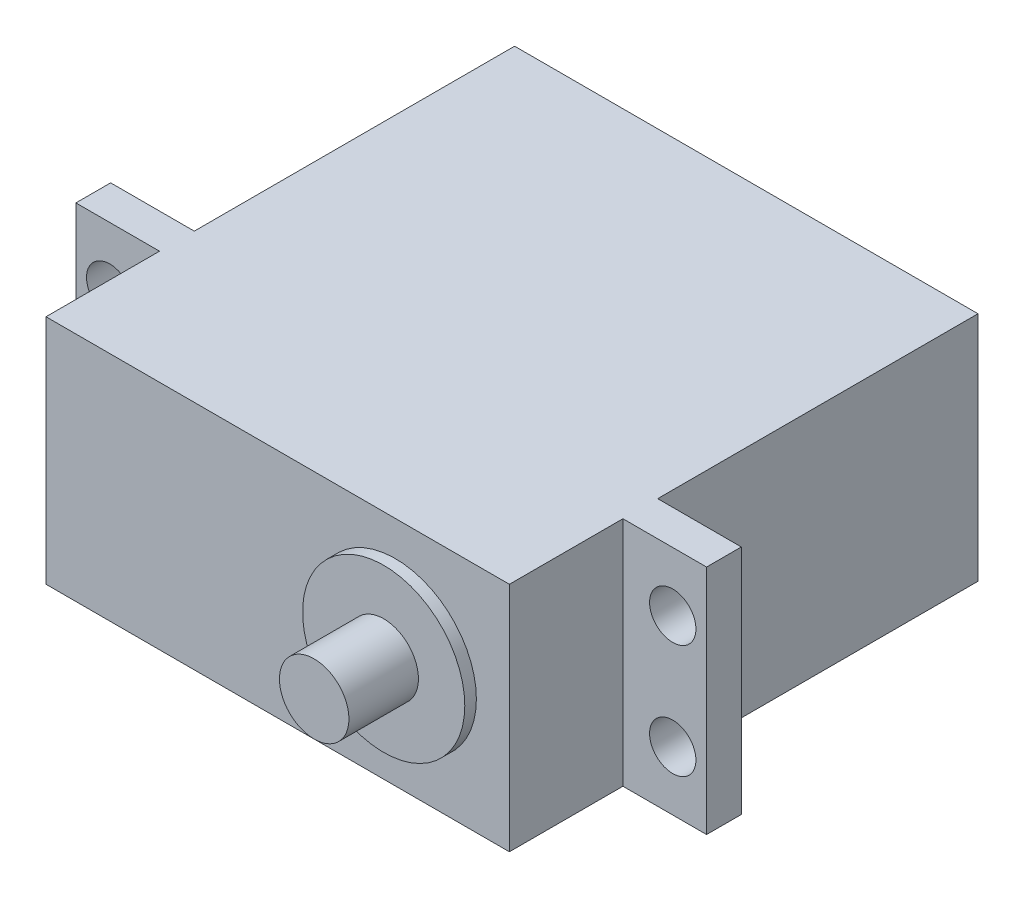
SolidWorks part; units mm, degrees
ref_plane "Front Plane" through (0, 0, 0) normal (0, 0, 1) x (1, 0, 0)
ref_plane "Top Plane" through (0, 0, 0) normal (0, 1, 0) x (1, 0, 0)
ref_plane "Right Plane" through (0, 0, 0) normal (1, 0, 0) x (0, 0, -1)
sketch "Sketch2" plane through (0, 0, 0) normal (0, 0, 1) x (1, 0, 0)
  line L1 (-13.5922, 208.3879) -> (-53.5922, 208.3879)
  line L2 (-13.5922, 208.3879) -> (-13.5922, 228.3879)
  line L3 (-13.5922, 228.3879) -> (-53.5922, 228.3879)
  line L4 (-53.5922, 208.3879) -> (-53.5922, 228.3879)
  dimension "D1" = 40
  dimension "D2" = 20
extrude "Boss-Extrude1" add sketch "Sketch2" along normal blind 27.65
sketch "Sketch3" plane through (0, 0, 27.65) normal (0, 0, 1) x (1, 0, 0)
  line L0 (-53.5922, 208.3879) -> (-13.5922, 208.3879) construction
  line L1 (-6.3722, 208.3879) -> (-60.8122, 208.3879)
  line L2 (-6.3722, 208.3879) -> (-6.3722, 228.3879)
  line L3 (-6.3722, 228.3879) -> (-60.8122, 228.3879)
  line L4 (-60.8122, 208.3879) -> (-60.8122, 228.3879)
  line L5 (-13.5922, 228.3879) -> (-53.5922, 228.3879) construction
  line L6 (-13.5922, 218.3879) -> (-53.5922, 218.3879) construction
  line L7 (-13.5922, 208.3879) -> (-13.5922, 228.3879) construction
  line L8 (-53.5922, 228.3879) -> (-53.5922, 208.3879) construction
  line L9 (-33.5922, 218.3879) -> (-33.5922, 214.2288) construction
  circle A0 centre (-9.2922, 213.4879) radius 2
  circle A1 centre (-9.2922, 223.2879) radius 2
  circle A2 centre (-57.8922, 223.2879) radius 2
  circle A3 centre (-57.8922, 213.4879) radius 2
  dimension "D1" = 0
  dimension "D2" = 0
  dimension "D3" = 54.44
  dimension "D4" = 27.22
extrude "Boss-Extrude2" add sketch "Sketch3" along normal blind 3
sketch "Sketch4" plane through (0, 0, 30.65) normal (0, 0, 1) x (1, 0, 0)
  line L4 (-13.5922, 208.3879) -> (-13.5922, 228.3879)
  line L5 (-53.5922, 208.3879) -> (-13.5922, 208.3879)
  line L6 (-53.5922, 228.3879) -> (-53.5922, 208.3879)
  line L7 (-13.5922, 228.3879) -> (-53.5922, 228.3879)
  line L8 (-13.5922, 208.3879) -> (-13.5922, 228.3879)
  line L9 (-53.5922, 208.3879) -> (-13.5922, 208.3879)
  line L10 (-53.5922, 228.3879) -> (-53.5922, 208.3879)
  line L11 (-13.5922, 228.3879) -> (-53.5922, 228.3879)
  dimension "D1" = 0
extrude "Boss-Extrude3" add sketch "Sketch4" along normal blind 9.8
sketch "Sketch5" plane through (0, 0, 40.45) normal (0, 0, 1) x (1, 0, 0)
  circle A0 centre (-23.4422, 218.3879) radius 7
  circle A1 centre (-57.8922, 223.2879) radius 2 construction
  dimension "D1" = 34.45
extrude "Boss-Extrude4" add sketch "Sketch5" along normal blind 1
sketch "Sketch6" plane through (0, 0, 41.45) normal (0, 0, 1) x (1, 0, 0)
  circle A0 centre (-23.4422, 218.3879) radius 3
extrude "Boss-Extrude5" add sketch "Sketch6" along normal blind 6
